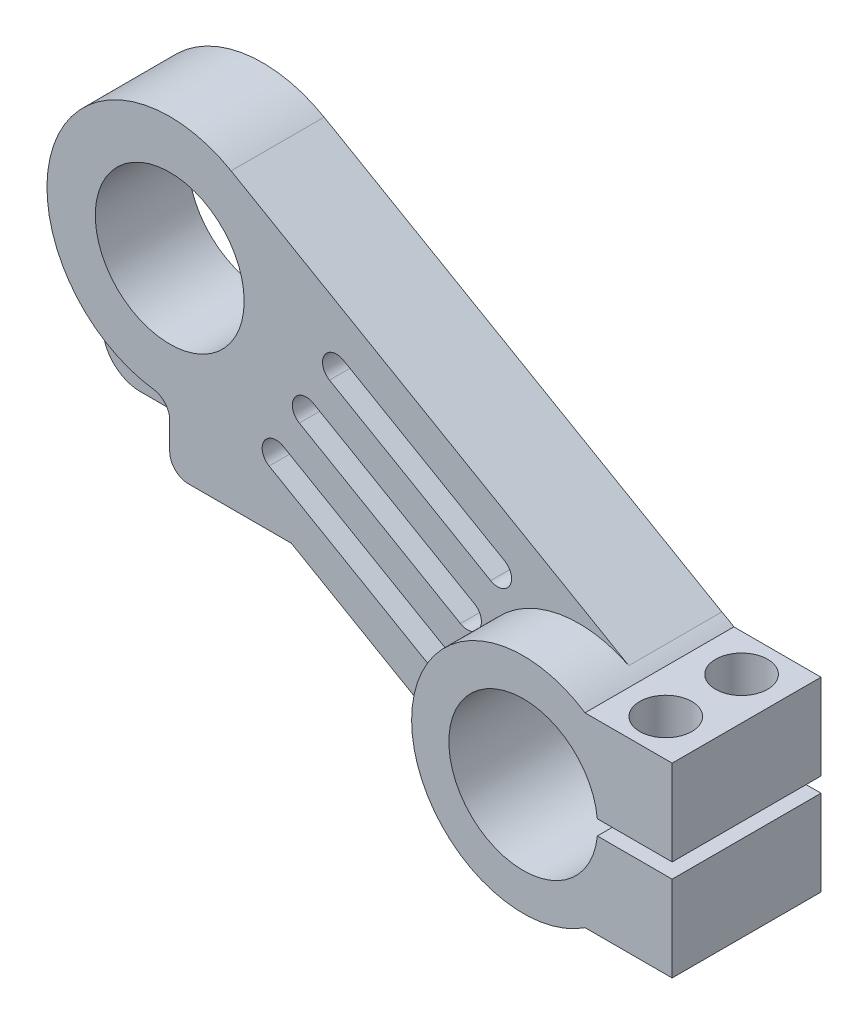
SolidWorks part; units mm, degrees
ref_plane "Alzado" through (0, 0, 0) normal (0, 0, 1) x (1, 0, 0)
ref_plane "Planta" through (0, 0, 0) normal (0, 1, 0) x (1, 0, 0)
ref_plane "Vista lateral" through (0, 0, 0) normal (1, 0, 0) x (0, 0, -1)
sketch "Croquis1" plane through (0, 0, 0) normal (0, 0, 1) x (1, 0, 0)
  line L0 (-285.961, 120) -> (-285.961, 40)
  line L1 (-210, 20) -> (-154.641, 20)
  line L2 (-30, -51.9615) -> (-154.641, 20)
  line L3 (-220, 44.7001) -> (-220, 30)
  line L4 (-187.0195, 177.1239) -> (26.7132, 53.7253)
  line L5 (-265.961, 20) -> (-210, 20)
  line L6 (80, -4) -> (80, -50)
  line L7 (33.1662, 50) -> (80, 50)
  line L9 (33.1662, -50) -> (80, -50)
  line L10 (80, 50) -> (80, 4)
  line L11 (39.7995, 4) -> (80, 4)
  line L13 (39.7995, -4) -> (80, -4)
  line L15 (-60, 34.5741) -> (-146.6025, 84.5741) construction
  line L16 (-63.75, 28.0789) -> (-150.3525, 78.0789)
  line L17 (-56.25, 41.0693) -> (-142.8525, 91.0693)
  line L18 (-76.221, 6.4785) -> (-162.8236, 56.4785) construction
  line L19 (-79.971, -0.0167) -> (-166.5736, 49.9833)
  line L20 (-72.471, 12.9736) -> (-159.0736, 62.9736)
  line L21 (-43.779, 62.6697) -> (-130.3815, 112.6697) construction
  line L22 (-47.529, 56.1745) -> (-134.1315, 106.1745)
  line L23 (-40.029, 69.1649) -> (-126.6315, 119.1649)
  line L24 (-89.971, -17.3372) -> (-30.029, 86.4854) construction
  arc A0 (39.7995, 4) -> (39.7995, -4) centre (0, 0) ccw
  circle A1 centre (-220, 120) radius 40
  arc A2 (33.1662, 50) -> (33.1662, -50) centre (0, 0) ccw
  arc A3 (-187.0195, 177.1239) -> (-228.6835, 54.6131) centre (-220, 120) ccw
  arc A4 (-285.961, 40) -> (-265.961, 20) centre (-265.961, 40) ccw
  arc A5 (-220, 44.7001) -> (-228.6835, 54.6131) centre (-230, 44.7001) ccw
  arc A6 (-210, 20) -> (-220, 30) centre (-210, 30) cw
  arc A7 (-63.75, 28.0789) -> (-56.25, 41.0693) centre (-60, 34.5741) ccw
  arc A8 (-142.8525, 91.0693) -> (-150.3525, 78.0789) centre (-146.6025, 84.5741) ccw
  arc A9 (-79.971, -0.0167) -> (-72.471, 12.9736) centre (-76.221, 6.4785) ccw
  arc A10 (-159.0736, 62.9736) -> (-166.5736, 49.9833) centre (-162.8236, 56.4785) ccw
  arc A11 (-47.529, 56.1745) -> (-40.029, 69.1649) centre (-43.779, 62.6697) ccw
  arc A12 (-126.6315, 119.1649) -> (-134.1315, 106.1745) centre (-130.3815, 112.6697) ccw
  point P16 (-285.961, 20)
  point P19 (-220, 54.039)
  point P28 (-103.3013, 59.5741)
  point P37 (-119.5223, 31.4785)
  point P44 (-87.0803, 87.6697)
  point P54 (-60, 34.5741)
  dimension "D1" = 80
  dimension "D2" = 60
  dimension "D3" = 220
  dimension "D5" = 65.961
  dimension "D8" = 20
  dimension "D9" = 10
  dimension "D10" = 10
  dimension "D17" = 15
  dimension "D4" = 120
  dimension "D6" = 150
  dimension "D7" = 100
  dimension "D11" = 100
  dimension "D12" = 80
  dimension "D13" = 46
  dimension "D14" = 46
  dimension "D15" = 60
  dimension "D16" = 100
  dimension "D18" = 20
  dimension "D19" = 20
extrude "Saliente-Extruir2" add sketch "Croquis1" along normal blind 50 contours A6 L1 L2 A2 L4 A3 A5 L3 A12 L23 A11 L22 A10 L20 A9 L19 A8 L17 A7 L16 A1 region at (-153.9666, 82.8591, 0)
extrude "Saliente-Extruir3" add sketch "Croquis1<4>" along normal blind 80 contours L7 A2 L9 L6 L13 A0 L11 L10 region at (29.0757, 50.366, 0)
sketch "Croquis1<4>" plane through (0, 0, 0) normal (0, 0, 1) x (1, 0, 0) same geometry as "Croquis1"
extrude "Saliente-Extruir4" add sketch "Croquis1<5>" along normal blind 20 contours L5 A6 L3 A5 A3 L0 A4 region at (-257.6209, 46.7535, 0)
sketch "Croquis1<5>" plane through (0, 0, 0) normal (0, 0, 1) x (1, 0, 0) same geometry as "Croquis1"
sketch "Croquis4" plane through (0, 50, 0) normal (0, 1, 0) x (1, 0, 0)
  line L0 (80, -80) -> (80, 0) construction
  line L1 (33.1662, -80) -> (80, -80) construction
  point P0 (57.3094, -20)
  point P1 (56.583, -60)
  dimension "D1" = 23.417
  dimension "D2" = 20
  dimension "D3" = 40
hole_wizard "Refrentado para tornillo con cabeza troncocónica de M52" positions "Croquis3D3" profile "Croquis7" counterbore size "M5" standard "Ansi Metric" end condition through all
sketch3d "Croquis3D3"
  point P0 (56.583, 50, 60)
  point P3 (57.3094, 50, 20)
sketch "Croquis7" plane through (56.583, 50, 60) normal (1, 0, 0) x (0, 0, 1)
  line L0 (0, 0) -> (0, 110)
  line L1 (0, 110) -> (8, 110)
  line L3 (8, 110) -> (8, 20)
  line L4 (8, 20) -> (14, 20)
  line L5 (14, 20) -> (14, 0)
  line L7 (14, 0) -> (0, 0)
  line L11 (0, -6.35) -> (0, 107.95) construction
  dimension "Diámetro de taladro hasta el siguiente" = 16
  dimension "Profundidad de taladro hasta el siguiente" = 110
  dimension "Diámetro de refrentado" = 28
  dimension "Profundidad de refrentado" = 20
